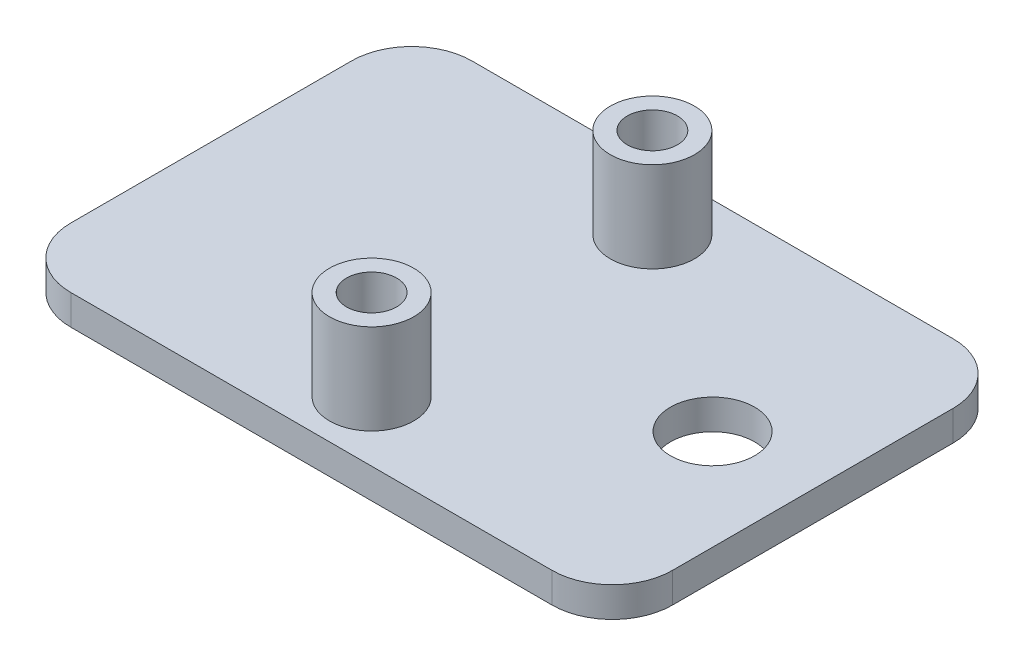
SolidWorks part; units mm, degrees
note: The reader was unsure of these and kept them because the rebuilt part matched: thickness of "基体-法兰1", "钣金6", "钣金7", "钣金8".
material "普通碳钢"
ref_plane "前视基准面" through (0, 0, 0) normal (0, 0, 1) x (1, 0, 0)
ref_plane "上视基准面" through (0, 0, 0) normal (0, 1, 0) x (1, 0, 0)
ref_plane "右视基准面" through (0, 0, 0) normal (1, 0, 0) x (0, 0, -1)
sketch "草图1" plane through (0, 0, 0) normal (0, 1, 0) x (1, 0, 0)
  line L0 (-21.42, 0) -> (20.9581, 0) construction
  line L1 (0, 18.9614) -> (0, -19.0199) construction
  line L2 (-7.3843, 10) -> (16.6157, 10)
  line L3 (19.6157, 7) -> (19.6157, -7)
  line L4 (16.6157, -10) -> (-7.3843, -10)
  line L5 (-10.3843, -7) -> (-10.3843, 7)
  circle A0 centre (14.6157, 0) radius 2.1
  arc A1 (-7.3843, 10) -> (-10.3843, 7) centre (-7.3843, 7) ccw
  arc A2 (-10.3843, -7) -> (-7.3843, -10) centre (-7.3843, -7) ccw
  arc A3 (16.6157, -10) -> (19.6157, -7) centre (16.6157, -7) ccw
  arc A4 (19.6157, 7) -> (16.6157, 10) centre (16.6157, 7) ccw
  dimension "D3" = 3
  dimension "D5" = 4.2
  dimension "D1" = 20
  dimension "D2" = 30
  dimension "D4" = 5
base flange "基体-法兰1" sketch "草图1" thickness 1.5 reverse thickness direction no parameters "D1"=1
sketch "草图2" plane through (0, 0, 0) normal (0, 1, 0) x (1, 0, 0)
  line L0 (-27.4749, 0) -> (37.7065, 0) construction
  line L1 (-10.3843, 7) -> (-10.3843, -7) construction
  circle A0 centre (4.6157, 7) radius 2.1
  circle A1 centre (4.6157, -7) radius 2.1
  dimension "D3" = 4.2
  dimension "D1" = 14
  dimension "D2" = 15
extrude "凸台-拉伸1" add sketch "草图2" along normal blind 4.5
hole_wizard "M3 螺纹孔1" positions "草图3" profile "草图4" tap size "M3" standard "GB"
sketch "草图3" plane through (0, 4.5, 0) normal (0, 1, 0) x (1, 0, 0)
  point P0 (4.6157, 7)
  point P3 (4.6157, -7)
sketch "草图4" plane through (4.6157, 4.5, -7) normal (1, 0, 0) x (0, 0, 1)
  line L0 (0, 0) -> (0, 4)
  line L1 (0, 4) -> (1.25, 4)
  line L2 (1.25, 4) -> (1.25, 0)
  line L5 (1.25, 0) -> (0, 0)
  line L10 (0, 4) -> (-1.25, 4) construction
  line L11 (0, -6.35) -> (0, 107.95) construction
  dimension "螺纹孔钻头直径" = 2.5
  dimension "螺纹孔钻头深度" = 4
  dimension "导头角度" = 180
cosmetic thread "孔螺蚊线1"
cosmetic thread "孔螺蚊线2"
sketch "折弯-线1" [suppressed] plane through (0, 0, 0) normal (0, 1, 0) x (1, 0, 0)
sketch "边界框1" [suppressed] plane through (0, 0, 0) normal (0, 1, 0) x (1, 0, 0)
sheet metal parameters "钣金6" thickness 1.5 parameters "D1"=1, "D7"=1.2
flat pattern "平板型式6" [suppressed]
sketch "折弯-线2" plane through (0, 0, 0) normal (0, 1, 0) x (1, 0, 0)
sketch3d "边界框2" [suppressed]
  line L0 (14.6157, 10, 0) -> (-10.3843, 10, 0) construction
  line L1 (14.6157, -10, 0) -> (-10.3843, -10, 0) construction
  line L2 (14.6157, 10, 0) -> (14.6157, -10, 0) construction
  line L3 (-10.3843, 10, 0) -> (-10.3843, -10, 0) construction
sheet metal parameters "钣金7" thickness 1.5 parameters "D1"=1, "D7"=1.2
flat pattern "平板型式6"
sketch "折弯-线2" plane through (0, 0, 0) normal (0, 1, 0) x (1, 0, 0)
sketch3d "边界框2" [suppressed]
  line L0 (14.6157, 10, 0) -> (-10.3843, 10, 0) construction
  line L1 (14.6157, -10, 0) -> (-10.3843, -10, 0) construction
  line L2 (14.6157, 10, 0) -> (14.6157, -10, 0) construction
  line L3 (-10.3843, 10, 0) -> (-10.3843, -10, 0) construction
sheet metal parameters "钣金8" thickness 1.5 parameters "D1"=1, "D7"=1.2
flat pattern "平板型式6"
sketch "折弯-线2" plane through (0, 0, 0) normal (0, 1, 0) x (1, 0, 0)
sketch3d "边界框2" [suppressed]
  line L0 (-3, -17, 0) -> (27, -17, 0) construction
  line L1 (-3, 3, 0) -> (27, 3, 0) construction
  line L2 (-3, -17, 0) -> (-3, 3, 0) construction
  line L3 (27, -17, 0) -> (27, 3, 0) construction
